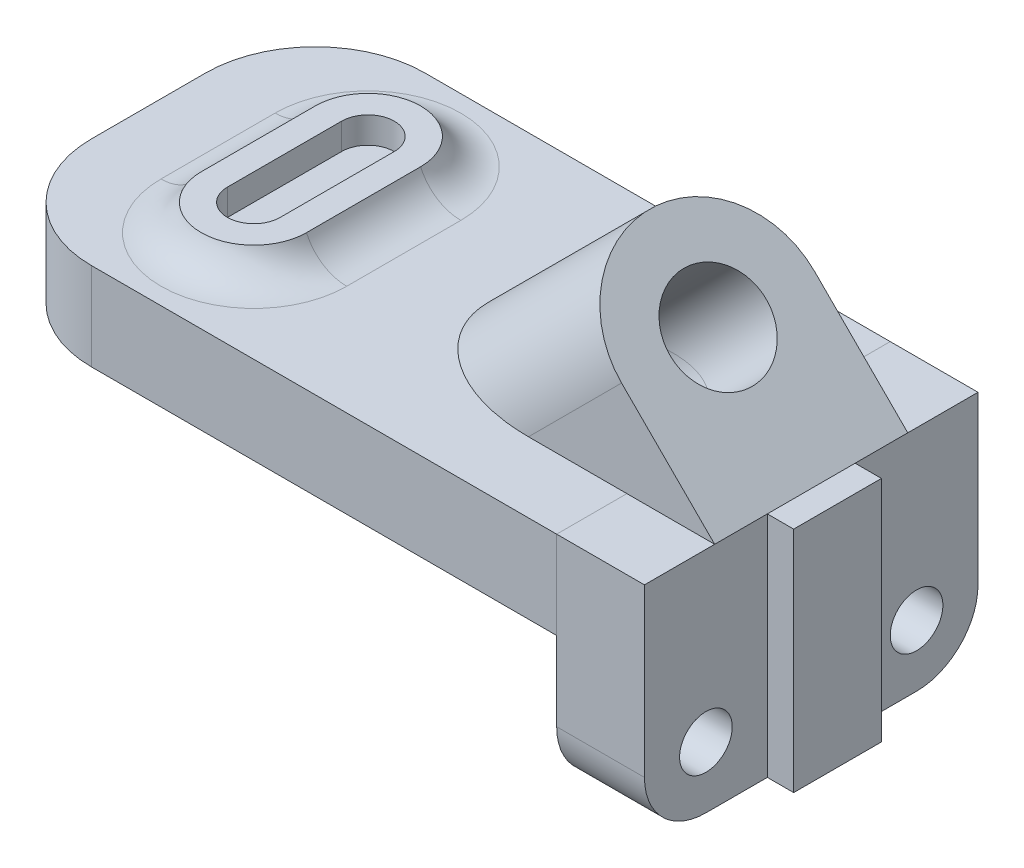
SolidWorks part; units mm, degrees
ref_plane "Front Plane" through (0, 0, 0) normal (0, 0, 1) x (1, 0, 0)
ref_plane "Top Plane" through (0, 0, 0) normal (0, 1, 0) x (1, 0, 0)
ref_plane "Right Plane" through (0, 0, 0) normal (1, 0, 0) x (0, 0, -1)
sketch "Sketch1" plane through (0, 0, 0) normal (0, 1, 0) x (1, 0, 0)
  line L0 (-70.023, 1.9044) -> (-70.023, -24.0956)
  line L1 (-45.023, 26.9044) -> (60.977, 26.9044)
  line L3 (-45.023, -49.0956) -> (60.977, -49.0956)
  line L4 (60.977, 26.9044) -> (60.977, -49.0956)
  arc A0 (-45.023, 26.9044) -> (-70.023, 1.9044) centre (-45.023, 1.9044) ccw
  arc A1 (-70.023, -24.0956) -> (-45.023, -49.0956) centre (-45.023, -24.0956) ccw
  dimension "D3" = 25
  dimension "D4" = 25
  dimension "D1" = 106
  dimension "D2" = 26
extrude "Boss-Extrude1" add sketch "Sketch1" along normal blind 20
sketch "Sketch2" plane through (0, 20, 0) normal (0, 1, 0) x (1, 0, 0)
  line L0 (-62.0649, -24.0956) -> (-33.023, -24.0956) construction
  line L2 (-45.023, 1.9044) -> (-45.023, -24.0956)
  line L4 (-21.023, 1.9044) -> (-21.023, -24.0956)
  line L5 (-61.2467, 1.9044) -> (13.1877, 1.9044) construction
  line L6 (-33.023, 13.9044) -> (-33.023, -36.0956) construction
  line L7 (-39.023, 1.9044) -> (-39.023, -24.0956)
  line L9 (-27.023, -24.0956) -> (-27.023, 1.9044)
  line L10 (-33.023, -24.0956) -> (29.3492, -24.0956) construction
  arc A0 (-45.023, 1.9044) -> (-21.023, 1.9044) centre (-33.023, 1.9044) cw
  arc A1 (-45.023, -24.0956) -> (-21.023, -24.0956) centre (-33.023, -24.0956) ccw
  arc A2 (-39.023, 1.9044) -> (-27.023, 1.9044) centre (-33.023, 1.9044) cw
  arc A3 (-39.023, -24.0956) -> (-27.023, -24.0956) centre (-33.023, -24.0956) ccw
  dimension "D2" = 12
  dimension "D4" = 12
  dimension "D1" = 26
extrude "Boss-Extrude2" add sketch "Sketch2" along normal blind 6 contours L2 A1 L4 A0 A3 L7 A2 L9 region at (-33.023, 20, -13.3498)
fillet "Fillet1" radius 10 4 edges at (-33.023, 20, -13.9044) (-45.023, 20, 11.0956) (-33.023, 20, 36.0956) (-21.023, 20, 11.0956)
sketch "Sketch3" plane through (0, 0, 49.0956) normal (0, 0, 1) x (1, 0, 0)
  line L1 (60.977, 20) -> (80.977, 20)
  line L2 (60.977, 20) -> (60.977, -32)
  line L3 (60.977, -32) -> (80.977, -32)
  line L4 (80.977, 20) -> (80.977, -32)
  dimension "D1" = 20
  dimension "D2" = 52
extrude "Boss-Extrude3" add sketch "Sketch3" against normal blind 76 separate body
fillet "Fillet2" radius 14 2 edges at (70.977, -32, -26.9044) (70.977, -32, 49.0956)
sketch "Sketch4" plane through (80.977, 0, 0) normal (1, 0, 0) x (0, 0, -1)
  line L0 (-35.0956, -32) -> (-35.0956, 20) construction
  line L1 (12.9044, -32) -> (12.9044, 20) construction
  line L2 (-49.0956, -18) -> (26.9044, -18) construction
  line L4 (26.9044, 20) -> (-49.0956, 20) construction
  line L5 (-21.0956, 20) -> (-1.0956, 20)
  line L6 (-21.0956, 20) -> (-21.0956, -32)
  line L7 (-21.0956, -32) -> (-1.0956, -32)
  line L8 (-1.0956, 20) -> (-1.0956, -32)
  line L9 (12.9044, -32) -> (-35.0956, -32) construction
  line L10 (-49.0956, -18) -> (-49.0956, 20) construction
  circle A0 centre (-35.0956, -18) radius 6
  circle A1 centre (12.9044, -18) radius 6
  point P12 (-11.0956, 20)
  line M5 (-35.0956, -32) -> (12.9044, -32)
  line M8 (26.9044, 20) -> (-49.0956, 20)
  dimension "D1" = 12
  dimension "D2" = 12
  dimension "D4" = 38
  dimension "D3" = 48
  dimension "D5" = 20
extrude "Boss-Extrude4" add sketch "Sketch4" along normal blind 6 contours L8 L6 M8 M5 region at (80.977, -6, 11.0956)
ref_plane "Plane1" through (50.4885, 50.4885, 0) normal (0.7071, 0.7071, 0) x (0.7071, -0.7071, 0)
sketch "Sketch5" plane through (50.4885, 50.4885, 0) normal (0.7071, 0.7071, 0) x (0.7071, -0.7071, 0)
  line L0 (43.1173, -21.0956) -> (43.1173, -49.0956) construction
  line L1 (43.1173, -33.0956) -> (13.1173, -33.0956)
  line L2 (43.1173, -33.0956) -> (43.1173, 10.9044)
  line L3 (43.1173, 10.9044) -> (13.1173, 10.9044)
  line L5 (43.1173, -49.0956) -> (28.9751, -49.0956) construction
  arc A0 (13.1173, -33.0956) -> (13.1173, 10.9044) centre (13.1173, -11.0956) cw
  point P7 (43.1173, -11.0956)
  dimension "D1" = 22
  dimension "D2" = 38
  dimension "D3" = 30
extrude "Boss-Extrude5" add sketch "Sketch5" against normal up to surface (30 mm away) separate body up to face at (-33.023, 20, 11.0956)
sketch "Sketch7" plane through (50.4885, 50.4885, 0) normal (0.7071, 0.7071, 0) x (0, 0, -1)
  line L0 (-33.0956, -43.1173) -> (10.9044, -43.1173) construction
  line L1 (-33.0956, -13.1173) -> (-33.0956, -43.1173) construction
  circle A0 centre (-11.0956, -13.1173) radius 11
  dimension "D3" = 22
  dimension "D1" = 30
  dimension "D2" = 22
hole_wizard "Ø20.0mm Dowel Hole1" positions "3DSketch2" profile "Sketch8" hole size "Ø20.0" standard "AS"
sketch3d "3DSketch2"
  point P0 (59.7638, 41.2132, 11.0956)
sketch "Sketch8" plane through (59.7638, 41.2132, 11.0956) normal (0, 0, 1) x (-0.7071, 0.7071, 0)
  line L0 (0, 0) -> (0, 38.6095)
  line L1 (0, 38.6095) -> (11, 32)
  line L2 (11, 32) -> (11, 0)
  line L5 (11, 0) -> (0, 0)
  line L10 (0, 38.6095) -> (-11, 32) construction
  line L11 (0, -6.35) -> (0, 107.95) construction
  dimension "Hole Dia." = 22
  dimension "Hole Depth" = 32
  dimension "Drill Angle" = 118
extrude "Cut-Extrude1" cut sketch "Sketch4<3>" against normal up to next (20 mm away) contours A0
sketch "Sketch4<3>" plane through (80.977, 0, 0) normal (1, 0, 0) x (0, 0, -1) same geometry as "Sketch4"
extrude "Cut-Extrude2" cut sketch "Sketch4<4>" against normal up to next (20 mm away) contours A1
sketch "Sketch4<4>" plane through (80.977, 0, 0) normal (1, 0, 0) x (0, 0, -1) same geometry as "Sketch4"
